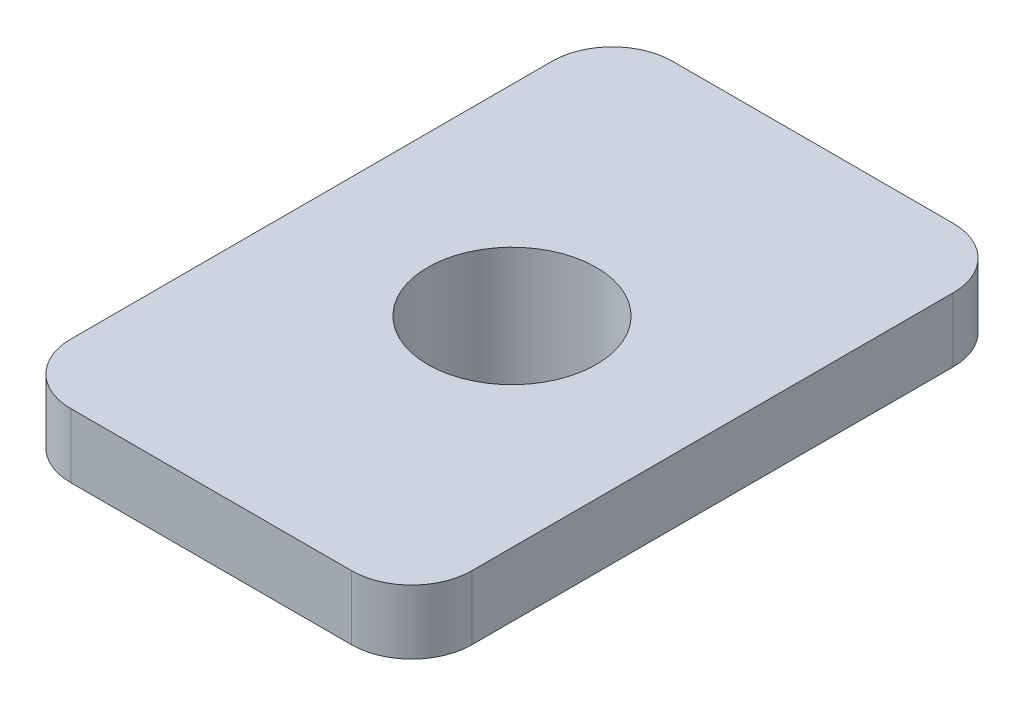
SolidWorks part; units mm, degrees
material "Plain Carbon Steel"
ref_plane "Front" through (0, 0, 0) normal (0, 0, 1) x (1, 0, 0)
ref_plane "Top" through (0, 0, 0) normal (0, 1, 0) x (1, 0, 0)
ref_plane "Right" through (0, 0, 0) normal (1, 0, 0) x (0, 0, -1)
sketch "Sketch1" plane through (0, 0, 0) normal (0, 1, 0) x (1, 0, 0)
  line L1 (0, 0) -> (10, 0)
  line L2 (0, 0) -> (0, 15)
  line L3 (0, 15) -> (10, 15)
  line L4 (10, 0) -> (10, 15)
  dimension "D1" = 15
  dimension "D2" = 10
extrude "Boss-Extrude1" add sketch "Sketch1" along normal blind 1.6
fillet "Fillet1" radius 1.5 4 edges at (0, 0.8, -15) (10, 0.8, -15) (0, 0.8, 0) (10, 0.8, 0)
sketch "Sketch2" plane through (0, 0, 0) normal (0, -1, 0) x (1, 0, 0)
  line L0 (0, -7.5) -> (5, -7.5) construction
  line L1 (0, -13.5) -> (0, -1.5) construction
  line L2 (5, -7.5) -> (5, -15) construction
  line L3 (8.5, -15) -> (1.5, -15) construction
  circle A0 centre (5, -7.5) radius 3.45
  dimension "D1" = 6.9
extrude "Boss-Extrude2" add sketch "Sketch2" along normal blind 1.4
hole_wizard "M5x0.8 Tapped Hole1" positions "Sketch5" profile "Sketch7" tap size "M5x0.8" standard "ANSI Metric" end condition through all
sketch "Sketch5" plane through (0, 1.6, 0) normal (0, 1, 0) x (1, 0, 0)
  point P0 (5, 7.5)
sketch "Sketch7" plane through (5, 1.6, -7.5) normal (1, 0, 0) x (0, 0, 1)
  line L0 (0, 0) -> (0, 3)
  line L1 (0, 3) -> (2.1, 3)
  line L2 (2.1, 3) -> (2.1, 0)
  line L5 (2.1, 0) -> (0, 0)
  line L11 (0, -6.35) -> (0, 107.95) construction
  dimension "Thru Tap Drill Dia." = 4.2
  dimension "Thru Tap Drill Depth" = 3
cosmetic thread "Hole Thread1" parameters "D2"=5
fillet "Fillet2" radius 0.4 1 edges at (5, 0, -10.95)
